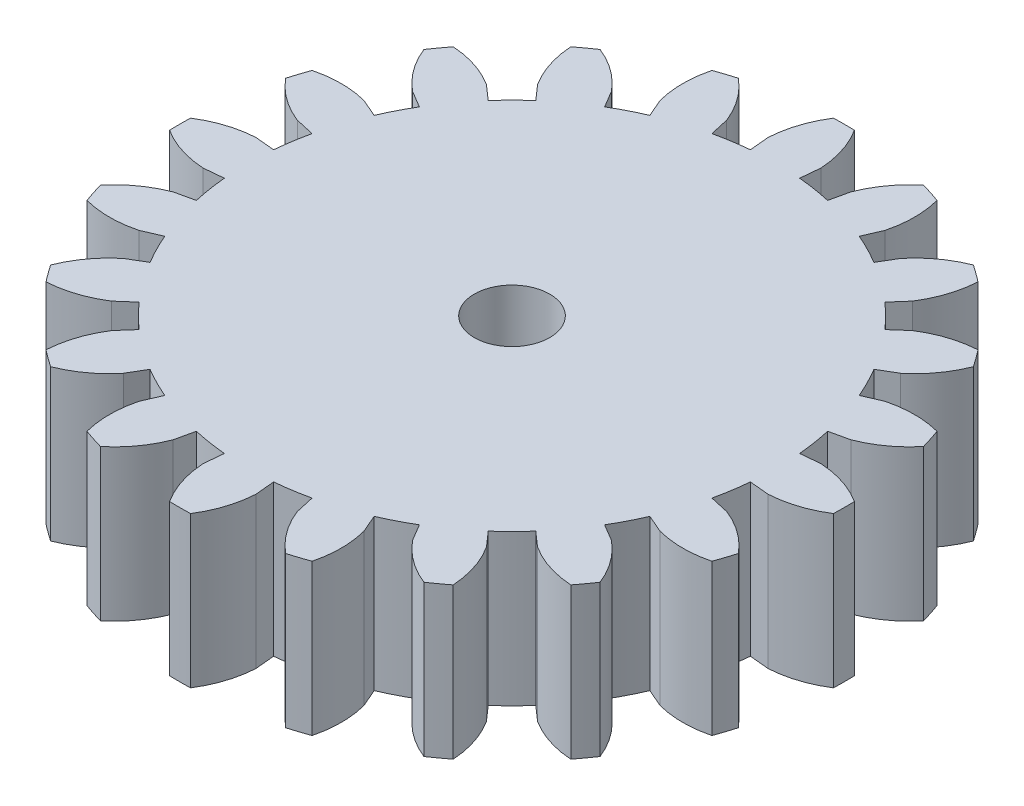
SolidWorks part; units mm, degrees
ref_plane "Спереди" through (0, 0, 0) normal (0, 0, 1) x (1, 0, 0)
ref_plane "Сверху" through (0, 0, 0) normal (0, 1, 0) x (1, 0, 0)
ref_plane "Справа" through (0, 0, 0) normal (1, 0, 0) x (0, 0, -1)
other "Configuration Table"
sketch "Эскиз1" plane through (0, 0, 0) normal (0, 1, 0) x (1, 0, 0)
  circle A0 centre (0, 0) radius 17.5
  dimension "D1" = 35
extrude "Бобышка-Вытянуть1" add sketch "Эскиз1" along normal blind 10
sketch "Эскиз2" plane through (0, 0, 0) normal (0, -1, 0) x (1, 0, 0)
  line L0 (0, 0) -> (0, 22) construction
  line L1 (0, 0) -> (-1.7523, 18.712) construction
  line L2 (0, 0) -> (1.7523, 18.712) construction
  line L5 (-1.5692, 19.9383) -> (0, 0) construction
  line L6 (0, 0) -> (1.5692, 19.9383) construction
  line L7 (-0.6949, 21.989) -> (0, 0) construction
  line L8 (-1.6317, 17.4238) -> (-1.7523, 18.712)
  line L9 (1.7523, 18.712) -> (1.6317, 17.4238)
  circle A0 centre (0, 0) radius 18.7938 construction
  circle A1 centre (0, 0) radius 20 construction
  circle A2 centre (0, 0) radius 22 construction
  arc A3 (-0.6949, 21.989) -> (0.6949, 21.989) centre (0, 0) cw
  arc A4 (-1.6317, 17.4238) -> (1.6317, 17.4238) centre (0, 0) cw
  circle A5 centre (0, 0) radius 17.5 construction
  arc A6 (-1.5692, 19.9383) -> (1.5692, 19.9383) centre (0, 0) cw construction
  arc A7 (-1.7523, 18.712) -> (-0.6949, 21.989) centre (5.0681, 18.3203) cw
  arc A8 (0.6949, 21.989) -> (1.7523, 18.712) centre (-5.0681, 18.3203) cw
  point P12 (0, 20)
  point P16 (0, 22)
  point P22 (0, 17.5)
  dimension "D1" = 37.5877
  dimension "D2" = 40
  dimension "D3" = 44
  dimension "D4" = 5.35
  dimension "D5" = 4.5
  dimension "D6" = 1.81
extrude "Бобышка-Вытянуть2" add sketch "Эскиз2" against normal blind 10
pattern_circular "Круговой массив1" count 20 over 360 about axis through (0, 10, 0) along (0, -1, 0) of "Бобышка-Вытянуть2" reverse direction yes
sketch "Эскиз3" plane through (0, 0, 0) normal (0, -1, 0) x (1, 0, 0)
  circle A0 centre (0, 0) radius 2.5
  dimension "D1" = 5
extrude "Вырез-Вытянуть1" cut sketch "Эскиз3" against normal through all
equation "\"Ширина груза\"= 160"
equation "\"Глубина груза\"= 240"
equation "\"Высота груза\"= 160"
equation "\"Ширина ячейки\"= \"Ширина груза\" + 10"
equation "\"Глубина ячейки\"= \"Глубина груза\" + 10"
equation "\"Высота ячейки\"= \"Высота груза\" + 10 + 13"
equation "\"Колво ячеек ширина\"= 2"
equation "\"Колво ячеек высота\"= 2"
equation "\"Толщина стенки\" = \"Толщина тонких панелей\""
equation "\"Крепление дверцы\"= 5 "
equation "\"Ширина рейки\"= \"Толщина шестерни\""
equation "\"Высота рейки\"= 20"
equation "\"Высота пола\" = 2*\"Толщина тонких панелей\""
equation "\"Колво полозьев\"= 5"
equation "\"Отступ рейки\"= 20"
equation "\"Глубина каретки\"= \"Глубина ячейки\" + 30 + \"Мотор Y высота корпуса\" + 20"
equation "\"Длинна рейки\" = (\"Ширина ячейки\"+\"Толщина вертикальных стенок\"+\"Крепление дверцы\")*\"Колво ячеек ширина\"+\"Ширина ячейки выгрузки\"*\"Колво выгрузки\"+\"Толщина вертикальных стенок\"+2*\"Отступ крепления мотора фиксации\"-\"Крепление дверцы\"*\"Колво ячеек ширина\""
equation "\"Отступ шпильки\"= 26"
equation "\"Диаметр шпильки\"= 5"
equation "\"Длинна шпильки\" = (\"Высота ячейки\"+\"Толщина горизонтальных плит\"+\"Высота пола\")*\"Колво ячеек высота\"+2*(\"Толщина горизонтальных плит\"+\"Отступ рейки\")"
equation "\"Ширина пластины\"= 50  "
equation "\"Высота зона выгрузки\"= \"Высота ячейки\" * 2 + \"Толщина стенки\" * 2"
equation "\"Колво выгрузки\"= 1"
equation "\"Ширина ячейки выгрузки\" = \"Ширина ячейки\"+\"Толщина вертикальных стенок\"+2*\"Отступ крепления мотора фиксации\""
equation "\"Отступ крепления мотора фиксации\" = (\"Ширина пластины\"+20-\"Толщина вертикальных стенок\")/2"
equation "\"Мотор X ширина корпуса\"= 42.3"
equation "\"Мотор X высота корпуса\"= 42.3"
equation "\"Мотор X длина корпуса\"= 40"
equation "\"Мотор X вылет вала\"= 19.8"
equation "\"Мотор Y ширина корпуса\"= 42.3"
equation "\"Мотор Y высота корпуса\"= 42.3"
equation "\"Мотор Y длина корпуса\"= 48"
equation "\"Мотор Y вылет вала\"= 30"
equation "\"Мотор Z ширина корпуса\"= 42"
equation "\"Мотор Z высота корпуса\"= 42"
equation "\"Мотор Z длина корпуса\"= 40"
equation "\"Мотор Z вылет вала\"= 23"
equation "\"Мотор диаметр вала ПРЕДВ\"= 5"
equation "\"Мотор шаг крепления ПРЕДВ\"= 31"
equation "\"Мотор диаметр отверстий ПРЕДВ\"= 3"
equation "\"Мотор глубина отверстий ПРЕДВ\"= 4.5"
equation "\"Мотор диаметр буртика ПРЕДВ\"= 22"
equation "\"Мотор высота буртика ПРЕДВ\"= 2"
equation "\"Мотор диаметр шкива ПРЕДВ\"= 16"
equation "\"Мотор длина шкива ПРЕДВ\"= 12"
equation "\"Мотор отступ шкива ПРЕДВ\"= 5"
equation "\"Мотор X шаг градусов\"= 1.8"
equation "\"Мотор Y шаг градусов\"= 1.8"
equation "\"Мотор Z шаг градусов\"= 1.8"
equation "\"Мотор Y диаметр ротора\"= 25.78"
equation "\"Толщина шестерни\"= 10"
equation "\"D1@Бобышка-Вытянуть1\"=\"Толщина шестерни\""
equation "\"D1@Бобышка-Вытянуть2\"=\"Толщина шестерни\""
equation "\"D1@Эскиз3\"=\"Мотор диаметр вала ПРЕДВ\""
equation "\"Толщина тонких панелей\" = 6"
equation "\"Толщина вертикальных стенок\" = 6"
equation "\"Толщина горизонтальных плит\" = 6"
equation "\"Базовая высота корпуса\"= (\"Высота ячейки\"+\"Толщина тонких панелей\"+\"Высота пола\")*\"Колво ячеек высота\"+6*\"Толщина тонких панелей\"+\"Мотор X ширина корпуса\"+\"Мотор Y ширина корпуса\"+75"
equation "\"Высота корпуса\"= (\"Высота ячейки\"+\"Толщина горизонтальных плит\"+\"Высота пола\")*\"Колво ячеек высота\"+2*\"Толщина горизонтальных плит\"+4*\"Толщина тонких панелей\"+\"Мотор X ширина корпуса\"+\"Мотор Y ширина корпуса\"+75"
equation "\"Смещение центра корпуса\"= (\"Высота корпуса\"-\"Базовая высота корпуса\")/2-(\"Толщина горизонтальных плит\"-\"Толщина тонких панелей\")"
equation "\"Отметка пола\"= -\"Базовая высота корпуса\"/2+\"Толщина тонких панелей\""
equation "\"Отметка потолка\"= \"Отметка пола\"+\"Высота корпуса\"-2*\"Толщина горизонтальных плит\""
equation "\"Отметка верхней полки\"= \"Отметка потолка\"-(28+\"Толщина тонких панелей\")-\"Высота ячейки\"-\"Высота пола\""
equation "\"Отметка нижней полки\"= \"Отметка верхней полки\"-\"Высота ячейки\"-\"Высота пола\"-\"Толщина горизонтальных плит\""
